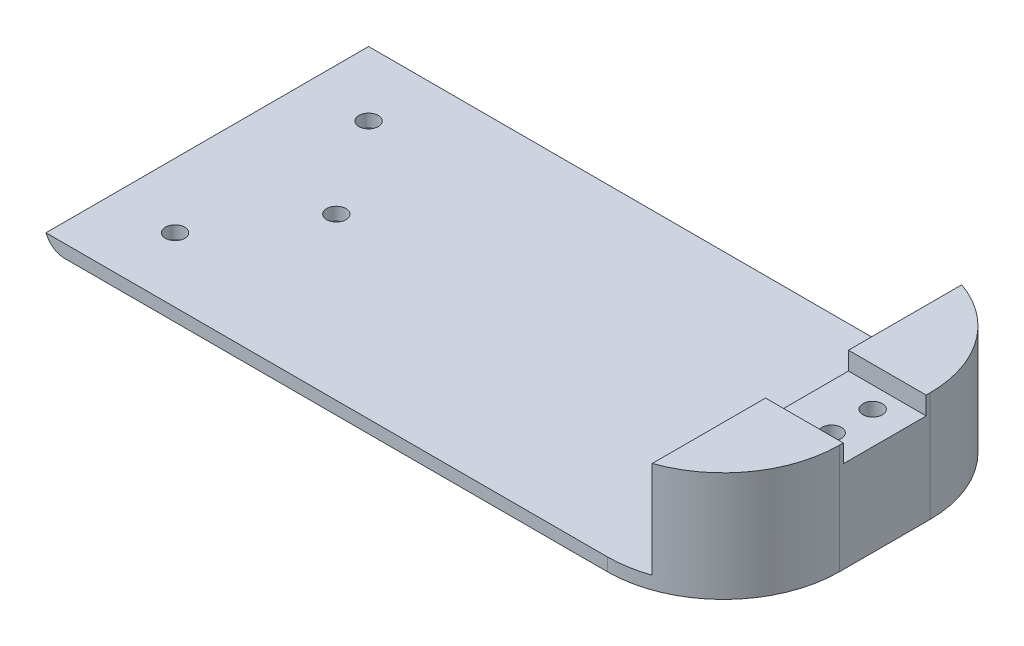
SolidWorks part; units mm, degrees
ref_plane "Front Plane" through (0, 0, 0) normal (0, 0, 1) x (1, 0, 0)
ref_plane "Top Plane" through (0, 0, 0) normal (0, 1, 0) x (1, 0, 0)
ref_plane "Right Plane" through (0, 0, 0) normal (1, 0, 0) x (0, 0, -1)
sketch "ProfileSketch1" plane through (0, 0, 0) normal (0, 0, 1) x (1, 0, 0)
  line L1 (105, 0) -> (105, -2)
  line L2 (105, -2) -> (0, -2)
  line L3 (0, -2) -> (0, 0)
  line L4 (0, 0) -> (92.95, 0)
  line L5 (92.95, 0) -> (92.95, 15)
  line L6 (92.95, 15) -> (105, 15)
  line L7 (105, 15) -> (105, 0)
  dimension "D1" = 105
  dimension "D2" = 2
  dimension "D3" = 15
  dimension "D4" = 12.05
extrude "Boss-Extrude1" add sketch "ProfileSketch1" along normal blind 50
sketch "MountHolesSketch2" plane through (0, 0, 0) normal (0, 1, 0) x (1, 0, 0)
  line L0 (92.95, 0) -> (0, 0) construction
  line L1 (92.95, -50) -> (0, -50) construction
  line L2 (0, -50) -> (0, 0) construction
  line L3 (92.95, -50) -> (92.95, 0) construction
  circle A0 centre (10, -10) radius 1.5
  circle A1 centre (10, -40) radius 1.5
  circle A2 centre (82.95, -25) radius 5
  circle A3 centre (20, -25) radius 1.5
  dimension "D1" = 3
  dimension "D6" = 10
  dimension "D2" = 10
  dimension "D3" = 10
  dimension "D4" = 10
  dimension "D5" = 10
  dimension "D7" = 25
  dimension "D8" = 10
extrude "MountHolesCut-Extrude1" cut sketch "MountHolesSketch2" against normal through all
sketch "MicroSwitchCutSketch3" plane through (0, 15, 0) normal (0, 1, 0) x (1, 0, 0)
  line L0 (92.95, -50) -> (92.95, 0) construction
  line L1 (92.95, -18.575) -> (105, -18.575)
  line L2 (92.95, -18.575) -> (92.95, -31.425)
  line L3 (92.95, -31.425) -> (105, -31.425)
  line L4 (105, -18.575) -> (105, -31.425)
  line L5 (105, -50) -> (105, 0) construction
  line L6 (105, 0) -> (92.95, 0) construction
  dimension "D1" = 12.85
  dimension "D2" = 18.575
extrude "MicroSwitchCut-Extrude2" cut sketch "MicroSwitchCutSketch3" against normal blind 2.8
sketch "MicroSwitchMountingHolesSketch4" plane through (0, 12.2, 0) normal (0, 1, 0) x (1, 0, 0)
  line L0 (92.95, -31.425) -> (105, -31.425) construction
  line L1 (105, -18.575) -> (92.95, -18.575) construction
  line L2 (92.95, -50) -> (92.95, 0) construction
  circle A0 centre (99.95, -28.175) radius 1.5
  circle A1 centre (99.95, -21.825) radius 1.5
  dimension "D4" = 3
  dimension "D1" = 3.25
  dimension "D2" = 3.25
  dimension "D3" = 7
extrude "MicroSwitchMountingHolesCut-Extrude3" cut sketch "MicroSwitchMountingHolesSketch4" against normal blind 3
fillet "RailEdgeFillet1" radius 3.125 1 edges at (0, -2, 25)
fillet "FrontEdgeFillet1" radius 18 2 edges at (105, 6.5, 0) (105, 6.5, 50)
equation "\"M3ScrewDiameter\"= 3mm"
equation "\"D1@MountHolesSketch2\" = \"M3ScrewDiameter\""
equation "\"YAxisMicroSwitchBlockWidth\"= 50mm"
equation "\"MicroSwitchLength\"= 12.85mm"
equation "\"MicroSwitchTerminalHeight\"= 3.5mm"
equation "\"MicroSwitchDepth\"= 2.8mm"
equation "\"MicroSwitchMountHoleOffsetFromSide\"= 3.25mm"
equation "\"MicroSwitchMountHoleOffsetFromBottom\"= 1.5mm"
equation "\"MicroSwitchExtraMountingHeight\"= 2mm"
equation "\"D1@Boss-Extrude1\"=\"YAxisMicroSwitchBlockWidth\""
equation "\"D7@MountHolesSketch2\" = \"YAxisMicroSwitchBlockWidth\" / 2"
equation "\"D1@MicroSwitchCutSketch3\" = \"MicroSwitchLength\""
equation "\"D2@MicroSwitchCutSketch3\" = \"YAxisMicroSwitchBlockWidth\" / 2 - \"MicroSwitchLength\" / 2"
equation "\"D1@MicroSwitchCut-Extrude2\" = \"MicroSwitchDepth\""
equation "\"D1@MicroSwitchMountingHolesSketch4\" = \"MicroSwitchMountHoleOffsetFromSide\""
equation "\"D2@MicroSwitchMountingHolesSketch4\" = \"MicroSwitchMountHoleOffsetFromSide\""
equation "\"D3@MicroSwitchMountingHolesSketch4\"=\"MicroSwitchExtraMountingHeight\" + \"MicroSwitchTerminalHeight\" + \"MicroSwitchMountHoleOffsetFromBottom\""
equation "\"M3HeatInsertHoleDiameter\"= 3mm'Spec"
equation "\"D4@MicroSwitchMountingHolesSketch4\" = \"M3HeatInsertHoleDiameter\""
equation "\"M3HeatInsertHoleDepth\"= 4mm"
equation "\"YAxisMicroSwitchMountingBlockHeight\"= 15mm"
equation "\"YAxisMicroSwitchSupportHeight\"= 2mm"
equation "\"D2@ProfileSketch1\"=\"YAxisMicroSwitchSupportHeight\""
equation "\"D3@ProfileSketch1\"=\"YAxisMicroSwitchMountingBlockHeight\""
equation "\"D4@ProfileSketch1\"=\"MicroSwitchExtraMountingHeight\" + \"MicroSwitchTerminalHeight\" + 6.55mm"
equation "\"MicroSwitchHeight\"= 6.55mm"
equation "\"M2HeatInsertDepth\"=3"
equation "\"D1@MicroSwitchMountingHolesCut-Extrude3\" = \"M2HeatInsertDepth\""
